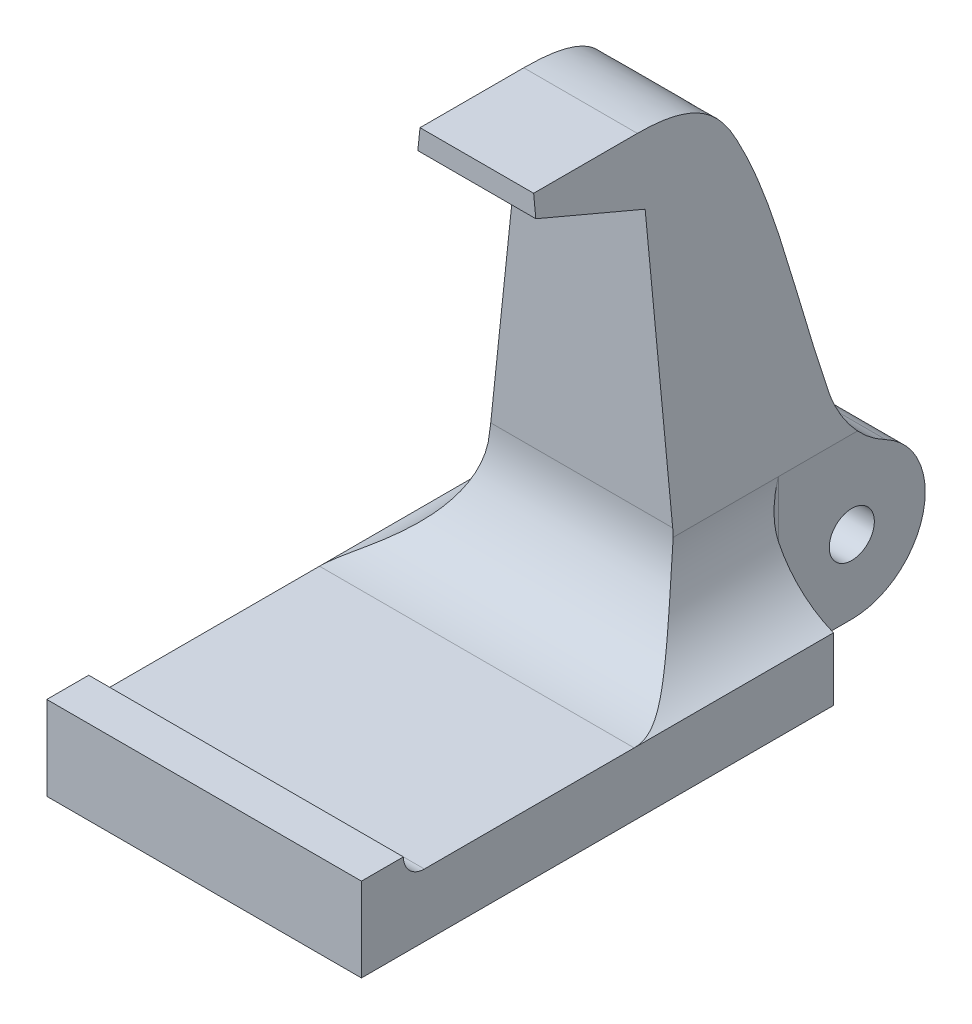
SolidWorks part; units mm, degrees
ref_plane "Front Plane" through (0, 0, 0) normal (0, 0, 1) x (1, 0, 0)
ref_plane "Top Plane" through (0, 0, 0) normal (0, 1, 0) x (1, 0, 0)
ref_plane "Right Plane" through (0, 0, 0) normal (1, 0, 0) x (0, 0, -1)
sketch "Sketch1" plane through (0, 0, 0) normal (0, 1, 0) x (1, 0, 0)
  line L0 (0, -64.9732) -> (0, 0) construction
  line L1 (-8.75, 0) -> (8.75, 0)
  line L2 (8.75, 0) -> (8.75, -15)
  line L3 (8.75, -15) -> (15, -15)
  line L4 (15, -15) -> (15, -60)
  line L5 (15, -60) -> (-15, -60)
  line L6 (-15, -15) -> (-15, -60)
  line L7 (-8.75, -15) -> (-15, -15)
  line L8 (-8.75, 0) -> (-8.75, -15)
  point P13 (0, -60)
  dimension "D1" = 30
  dimension "D2" = 45
  dimension "D3" = 15
  dimension "D4" = 17.5
extrude "Boss-Extrude1" add sketch "Sketch1" along normal blind 6
sketch "Sketch3" plane through (-8.75, 0, 0) normal (-1, 0, 0) x (0, 0, 1)
  line L10 (14, 6) -> (14, 7)
  line L11 (0, 7) -> (0, 6)
  line L12 (0, 0) -> (15, 0) construction
  line L13 (14, 6) -> (0, 6)
  line L14 (0, 6) -> (15, 6) construction
  arc A0 (14, 7) -> (0, 7) centre (7, 7) ccw
  dimension "D2" = 7
  dimension "D1" = 7
extrude "Boss-Extrude2" add sketch "Sketch3" against normal up to surface (17.5 mm away) up to face at (8.75, 3, 7.5)
sketch "Sketch5" plane through (-8.75, 0, 0) normal (-1, 0, 0) x (0, 0, 1)
  line L0 (7, 14) -> (7, 0) construction
  line L1 (0, 0) -> (15, 0) construction
  arc A0 (14, 7) -> (0, 7) centre (7, 7) ccw construction
  circle A1 centre (7, 7) radius 2.15
  dimension "D1" = 4.3
  dimension "D2" = 7
extrude "Cut-Extrude1" cut sketch "Sketch5" against normal up to surface (17.5 mm away) up to face at (8.75, 5.5, 9.6667)
fillet "Fillet1" radius 7 1 edges at (0, 0, 0)
sketch "Sketch6" plane through (0, 6, 0) normal (0, 1, 0) x (1, 0, 0)
  line L0 (0, -60) -> (0, 0) construction
  line L1 (-15, -60) -> (15, -60) construction
  line L2 (8.75, 0) -> (-8.75, 0) construction
  line L3 (2.25, -15) -> (-2.25, -15)
  line L4 (2.25, -15) -> (2.25, 0)
  line L5 (2.25, 0) -> (-2.25, 0)
  line L6 (-2.25, -15) -> (-2.25, 0)
  line L7 (2.25, -15) -> (-2.25, 0) construction
  line L8 (2.25, 0) -> (-2.25, -15) construction
  line L10 (8.75, -15) -> (-8.75, -15) construction
  point P5 (0, -7.5)
  dimension "D1" = 4.5
extrude "Cut-Extrude3" cut sketch "Sketch6" along normal blind 8 and the other way blind 8
sketch "Sketch7" plane through (8.75, 0, 0) normal (1, 0, 0) x (0, 0, -1)
  line L0 (-24, 6) -> (-24, 41)
  line L1 (-60, 6) -> (-15, 6) construction
  line L2 (-24, 41) -> (-34, 41)
  line L3 (-34, 41) -> (-34, 47)
  line L4 (-34, 47) -> (-24.1105, 47)
  line L6 (-14, 6) -> (-14, 7)
  line L8 (-24, 6) -> (-14, 6)
  line L10 (-19.2414, 47) -> (-2.1273, 47) construction
  arc A0 (-14, 7) -> (-7.1795, 13.9977) centre (-7, 7) cw
  circle A3 centre (-7, 7) radius 2.15 construction
  circle A4 centre (-7, 7) radius 2.15 construction
  arc A6 (0, 7) -> (-14, 7) centre (-7, 7) ccw construction
  spline S0 degree 3 poles (-24.1105, 47) (-17.8893, 47) (-11.6942, 37.8193) (-10.867, 25.4552) (-7.1795, 13.9977) knots 0 0 0 0 0.265029 1 1 1 1
  dimension "D5" = 0
  dimension "D1" = 10
  dimension "D2" = 35
  dimension "D3" = 6
  dimension "D4" = 10
extrude "Boss-Extrude3" add sketch "Sketch7" against normal up to surface (17.5 mm away) up to face at (-8.75, 7, 9.15)
sketch "Sketch8" plane through (-2.25, 0, 0) normal (1, 0, 0) x (0, 0, -1)
  line L3 (-15, 6) -> (-15, 7)
  line L5 (-7, 15) -> (-7, 7)
  line L6 (-15, 6) -> (-7, 6)
  line L7 (-7, 6) -> (-7, 7)
  arc A0 (-15, 7) -> (-7, 15) centre (-7, 7) cw
extrude "Cut-Extrude4" cut sketch "Sketch8" along normal up to surface (4.5 mm away) up to face at (2.25, 5.9213, 10.0967)
fillet "Fillet3" radius 10 3 edges at (0, 6, 24) (8.75, 6, 19.5) (-8.75, 6, 19.5)
fillet "Fillet6" radius 1 2 edges at (8.75, 7.6351, 15) (-8.75, 7.6351, 15)
fillet "Fillet7" radius 10 1 edges at (5.5, 13.9977, 7.1795)
ref_plane "Plane1" through (-10.2418, 1.0765, 0) normal (0.9945, -0.1045, 0) x (0, 0, 1)
sketch "Sketch9" plane through (-10.2418, 1.0765, 0) normal (0.9945, -0.1045, 0) x (0, 0, 1)
  line L1 (6.3535, -13.5188) -> (38.0706, -13.5188)
  line L2 (6.3535, -13.5188) -> (6.3535, -53.3281)
  line L3 (6.3535, -53.3281) -> (38.0706, -53.3281)
  line L4 (38.0706, -13.5188) -> (38.0706, -53.3281)
extrude "Cut-Extrude5" cut sketch "Sketch9" against normal blind 10
mirror "Mirror1" about plane through (0, 0, 0) normal (1, 0, 0) of "Cut-Extrude5"
sketch "Sketch10" plane through (15, 0, 0) normal (1, 0, 0) x (0, 0, -1)
  line L0 (-60, 6) -> (-60, 8)
  line L1 (-60, 8) -> (-56, 8)
  line L2 (-56, 8) -> (-56, 6)
  line L3 (-60, 6) -> (-34, 6) construction
  line L4 (-56, 6) -> (-60, 6)
  dimension "D1" = 4
  dimension "D2" = 2
extrude "Boss-Extrude4" add sketch "Sketch10" against normal up to surface (30 mm away) up to face at (-15, 3.6, 36.8)
fillet "Fillet8" radius 2 1 edges at (0, 6, 56)
chamfer "Chamfer1" distance 10 distance2 4 1 edges at (0, 41, 34) first distance on face at (0, 41, 29)
